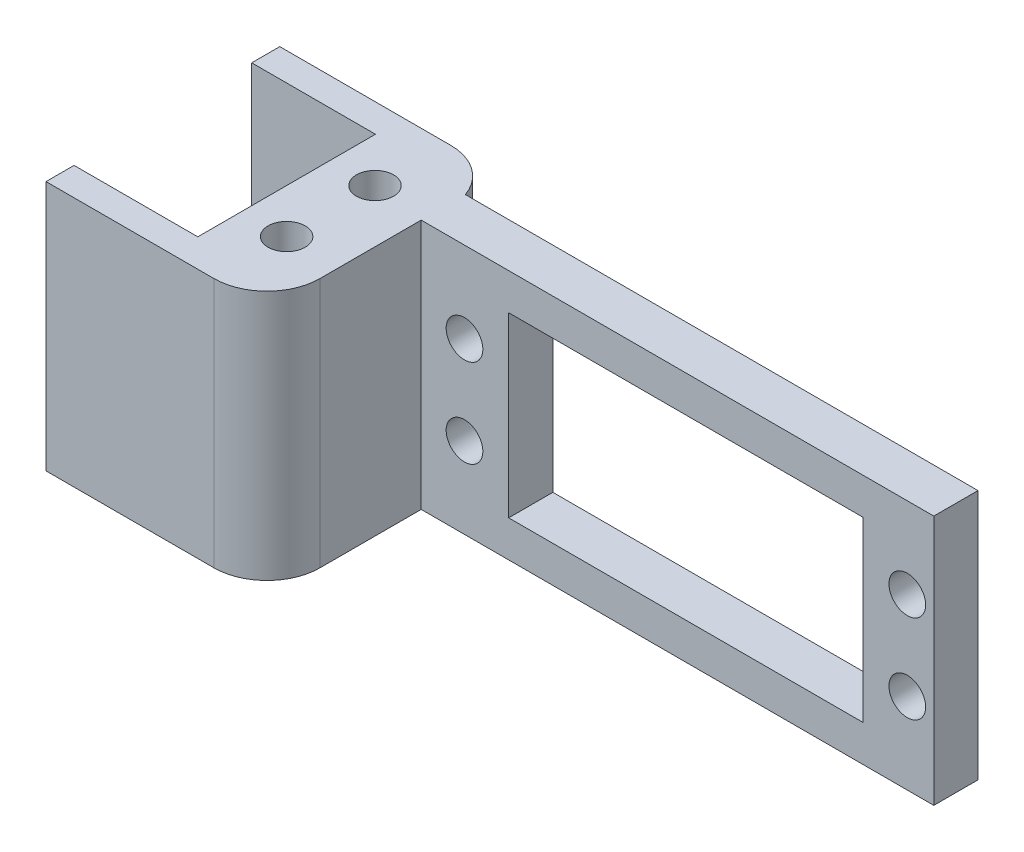
SolidWorks part; units mm, degrees
ref_plane "Front Plane" through (0, 0, 0) normal (0, 0, 1) x (1, 0, 0)
ref_plane "Top Plane" through (0, 0, 0) normal (0, 1, 0) x (1, 0, 0)
ref_plane "Right Plane" through (0, 0, 0) normal (1, 0, 0) x (0, 0, -1)
sketch "Sketch1" plane through (0, 0, 0) normal (0, 1, 0) x (1, 0, 0)
  line L0 (0, 0) -> (14, 0)
  line L1 (14, 0) -> (14, -20.1)
  line L2 (14, -20.1) -> (0, -20.1)
  line L3 (0, -20.1) -> (0, -23.275)
  line L4 (0, -23.275) -> (25, -23.275)
  line L5 (25, -23.275) -> (25, 3.175)
  line L6 (25, 3.175) -> (0, 3.175)
  line L7 (0, 3.175) -> (0, 0)
  line L8 (19, -5.05) -> (19, -15.05) construction
  circle A0 centre (19, -5.05) radius 2.1
  circle A1 centre (19, -15.05) radius 2.1
  point P13 (19, -10.05)
  point P14 (14, -10.05)
  dimension "D1" = 4.2
  dimension "D2" = 10
  dimension "D3" = 3.175
  dimension "D4" = 14
  dimension "D5" = 5
  dimension "D6" = 20.1
  dimension "D7" = 25
extrude "Boss-Extrude1" add sketch "Sketch1" along normal blind 28.35
sketch "Sketch2" plane through (25, 0, 0) normal (1, 0, 0) x (0, 0, -1)
  line L0 (3.175, 28.35) -> (3.175, 0) construction
  line L1 (-0.825, 28.35) -> (-5.825, 28.35)
  line L2 (-0.825, 28.35) -> (-0.825, 0)
  line L3 (-0.825, 0) -> (-5.825, 0)
  line L4 (-5.825, 28.35) -> (-5.825, 0)
  line L5 (-0.825, 28.35) -> (-5.825, 0) construction
  line L6 (-0.825, 0) -> (-5.825, 28.35) construction
  line L7 (-23.275, 28.35) -> (3.175, 28.35) construction
  point P0 (-3.325, 14.175)
  point P5 (3.175, 14.175)
  dimension "D1" = 4
  dimension "D2" = 5
extrude "Boss-Extrude2" add sketch "Sketch2" along normal blind 58
sketch "Sketch3" plane through (0, 0, 0.825) normal (0, 0, -1) x (-1, 0, 0)
  line L0 (-83, 0) -> (-83, 28.35) construction
  line L1 (-34.9, 4.125) -> (-75, 4.125)
  line L2 (-34.9, 4.125) -> (-34.9, 24.225)
  line L3 (-34.9, 24.225) -> (-75, 24.225)
  line L4 (-75, 4.125) -> (-75, 24.225)
  line L5 (-34.9, 4.125) -> (-75, 24.225) construction
  line L6 (-34.9, 24.225) -> (-75, 4.125) construction
  line L7 (-83, 0) -> (-83, 28.35) construction
  point P0 (-54.95, 14.175)
  point P5 (-83, 14.175)
  dimension "D1" = 20.1
  dimension "D2" = 40.1
  dimension "D3" = 8
extrude "Cut-Extrude1" cut sketch "Sketch3" against normal through all both and the other way through all
sketch "Sketch4" plane through (0, 0, 0.825) normal (0, 0, -1) x (-1, 0, 0)
  arc A0 (-81.8181, 18.175) -> (-81.8181, 20.175) centre (-80, 19.175) ccw construction
  arc A1 (-81.8181, 8.175) -> (-81.8181, 10.175) centre (-80, 9.175) ccw construction
  arc A2 (-28.0819, 20.175) -> (-28.0819, 18.175) centre (-29.9, 19.175) ccw construction
  arc A3 (-28.0819, 10.175) -> (-28.0819, 8.175) centre (-29.9, 9.175) ccw construction
  arc A4 (-81.8181, 18.175) -> (-81.8181, 20.175) centre (-80, 19.175) ccw construction
  arc A5 (-81.8181, 8.175) -> (-81.8181, 10.175) centre (-80, 9.175) ccw construction
  arc A6 (-28.0819, 20.175) -> (-28.0819, 18.175) centre (-29.9, 19.175) ccw construction
  arc A7 (-28.0819, 10.175) -> (-28.0819, 8.175) centre (-29.9, 9.175) ccw construction
  circle A8 centre (-29.9, 19.175) radius 2.075
  circle A9 centre (-29.9, 9.175) radius 2.075
  circle A10 centre (-80, 19.175) radius 2.075
  circle A11 centre (-80, 9.175) radius 2.075
extrude "Cut-Extrude2" cut sketch "Sketch4" against normal through all both and the other way through all
fillet "Fillet1" radius 6 2 edges at (25, 14.175, 23.275) (25, 14.175, -3.175)
